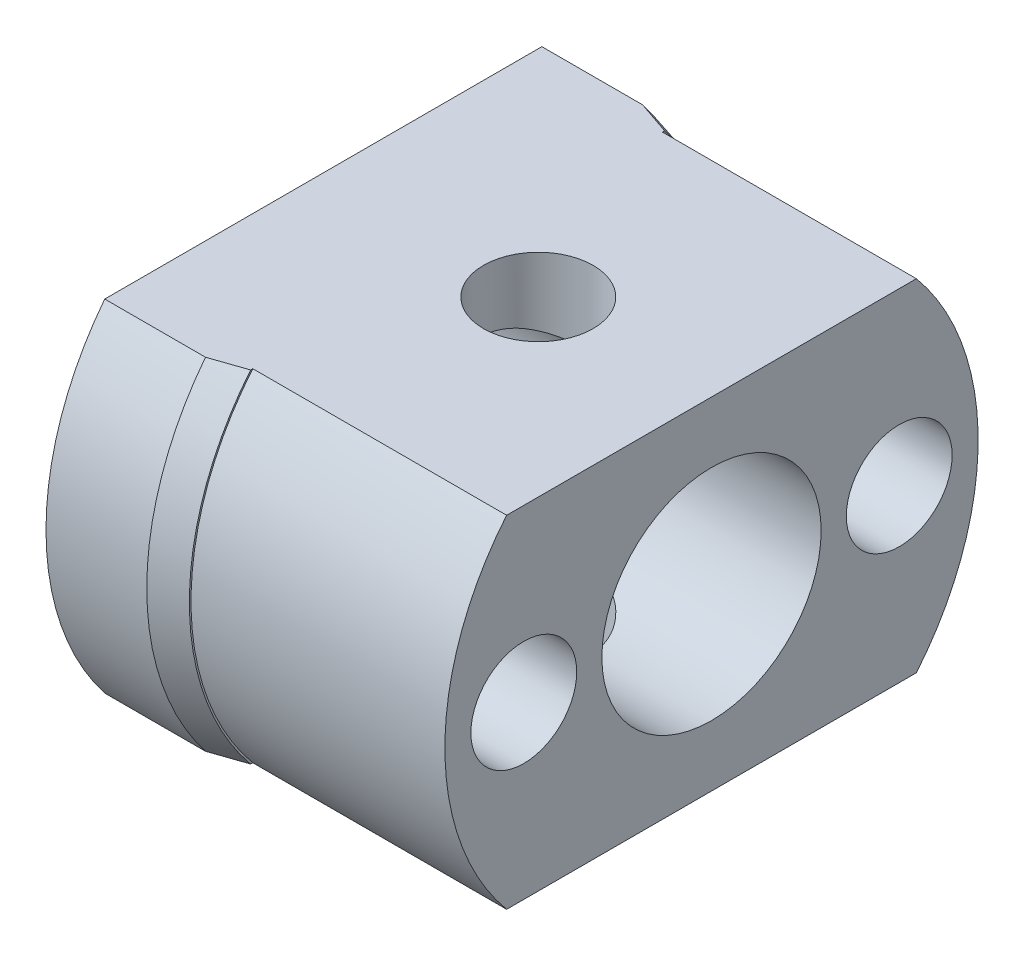
SolidWorks part; units mm, degrees
ref_plane "Front Plane" through (0, 0, 0) normal (0, 0, 1) x (1, 0, 0)
ref_plane "Top Plane" through (0, 0, 0) normal (0, 1, 0) x (1, 0, 0)
ref_plane "Right Plane" through (0, 0, 0) normal (1, 0, 0) x (0, 0, -1)
sketch "Sketch1" plane through (0, 0, 0) normal (1, 0, 0) x (0, 0, -1)
  line L0 (0, 0) -> (0, 0.7417) construction
  line L1 (-3.2639, 0) -> (-6.35, 0) construction
  circle A0 centre (0, 0) radius 6.35
  circle A1 centre (0, 0) radius 6.35
  circle A2 centre (0, 0) radius 3.2639
  circle A3 centre (-5.588, 0) radius 1.575
  circle A5 centre (0, 0) radius 7.9375
  circle A6 centre (5.588, 0) radius 1.575
  dimension "D1" = 12.7
  dimension "D2" = 6.5278
  dimension "D3" = 3.15
  dimension "D4" = 15.875
  dimension "D5" = 11.176
extrude "Inner Side Extrude" add sketch "Sketch1" along normal blind 2.032 contours A0 A2 A3 A6 | A5 A1 A6 A3 region at (0, 0, -3.8358) region at (0, 0, 7.713)
extrude "Outer Side Extrude" add sketch "Sketch1<3>" against normal blind 9.525 contours A0 A2 A3 A6 | A5 A0 region at (0, 0, -3.8358) region at (0, 0, 7.713)
sketch "Sketch1<3>" plane through (0, 0, 0) normal (1, 0, 0) x (0, 0, -1) same geometry as "Sketch1"
sketch "Sketch2" plane through (0, 0, 0) normal (0, 1, 0) x (1, 0, 0)
  line L0 (-9.525, 7.9375) -> (-9.525, -7.9375) construction
  line L1 (-9.525, 0) -> (0, 0) construction
  line L2 (2.032, -7.9375) -> (2.032, 7.9375) construction
  circle A0 centre (-3.1242, 0) radius 1.632
  point P0 (-9.525, 0)
  dimension "D1" = 3.2639
  dimension "D2" = 5.1562
extrude "Clevis Pin Cut" cut sketch "Sketch2" against normal through all and the other way through all
chamfer "Chamfer so Steve Doesn't cut himself" [suppressed] distance 0.3969 angle 45
sketch "Sketch3" plane through (-9.525, 0, 0) normal (1, 0, 0) x (0, 0, -1)
  circle A0 centre (0, 0) radius 8.255
  circle A6 centre (0, 0) radius 7.9375
  circle A7 centre (0, 0) radius 7.9375 construction
  dimension "D1" = 16.51
extrude "Boss-Extrude1" add sketch "Sketch3" along normal blind 4
sketch "Sketch4" plane through (-9.525, 0, 0) normal (1, 0, 0) x (0, 0, -1)
  line L0 (0, 0) -> (0, 1.7726)
  line L1 (-5.588, 2.5981) -> (-7.838, 1.299)
  line L2 (-7.838, 1.299) -> (-7.838, -1.299)
  line L3 (-7.838, -1.299) -> (-5.588, -2.5981)
  line L4 (-5.588, -2.5981) -> (-3.338, -1.299)
  line L5 (-3.338, -1.299) -> (-3.338, 1.299)
  line L6 (-3.338, 1.299) -> (-5.588, 2.5981)
  line L7 (3.338, 1.299) -> (5.588, 2.5981)
  line L8 (3.338, -1.299) -> (3.338, 1.299)
  line L9 (5.588, -2.5981) -> (3.338, -1.299)
  line L10 (7.838, -1.299) -> (5.588, -2.5981)
  line L11 (7.838, 1.299) -> (7.838, -1.299)
  line L12 (5.588, 2.5981) -> (7.838, 1.299)
  circle A0 centre (-5.588, 0) radius 2.25 construction
  circle A1 centre (5.588, 0) radius 2.25 construction
  circle M22 centre (5.588, 0) radius 1.575
  circle M24 centre (-5.588, 0) radius 1.575
  dimension "D1" = 4.5
extrude "Cut-Extrude1" cut sketch "Sketch4" along normal blind 4 contours L6 L5 L4 L3 L2 L1 M24 | L7 L12 L11 L10 L9 L8 M22 region at (-9.525, 1.889, 4.4974) region at (-9.525, 1.889, -4.4974)
chamfer "Chamfer1" distance 1 angle 15 1 edges at (-5.525, 0, -8.255) first distance on face at (-5.525, 0, -8.255)
sketch "Sketch5" plane through (0, 0, 0) normal (0, 0, 1) x (1, 0, 0)
  line L0 (-3.1242, -5.08) -> (-3.1242, 5.08)
  line L1 (-1.4923, 0) -> (-4.7562, 0) construction
  line L2 (6.3564, 0) -> (-6.3564, 0) construction
  line L3 (-11.3792, 9.3929) -> (5.1308, 9.3929)
  line L4 (-11.3792, 9.3929) -> (-11.3792, 5.08)
  line L5 (-11.3792, 5.08) -> (5.1308, 5.08)
  line L6 (5.1308, 9.3929) -> (5.1308, 5.08)
  line L7 (5.1308, -9.3929) -> (5.1308, -5.08)
  line L8 (-11.3792, -5.08) -> (5.1308, -5.08)
  line L9 (-11.3792, -9.3929) -> (-11.3792, -5.08)
  line L10 (-11.3792, -9.3929) -> (5.1308, -9.3929)
  point P8 (0, 0)
  point P17 (-3.1242, 0)
  dimension "D1" = 16.51
  dimension "D2" = 5.08
extrude "Cut-Extrude2" cut sketch "Sketch5" against normal through all both and the other way through all contours L6 L3 L4 L5 | L9 L10 L7 L8 region at (-3.1242, 7.2364, 0) region at (-3.1242, -7.2364, 0)
